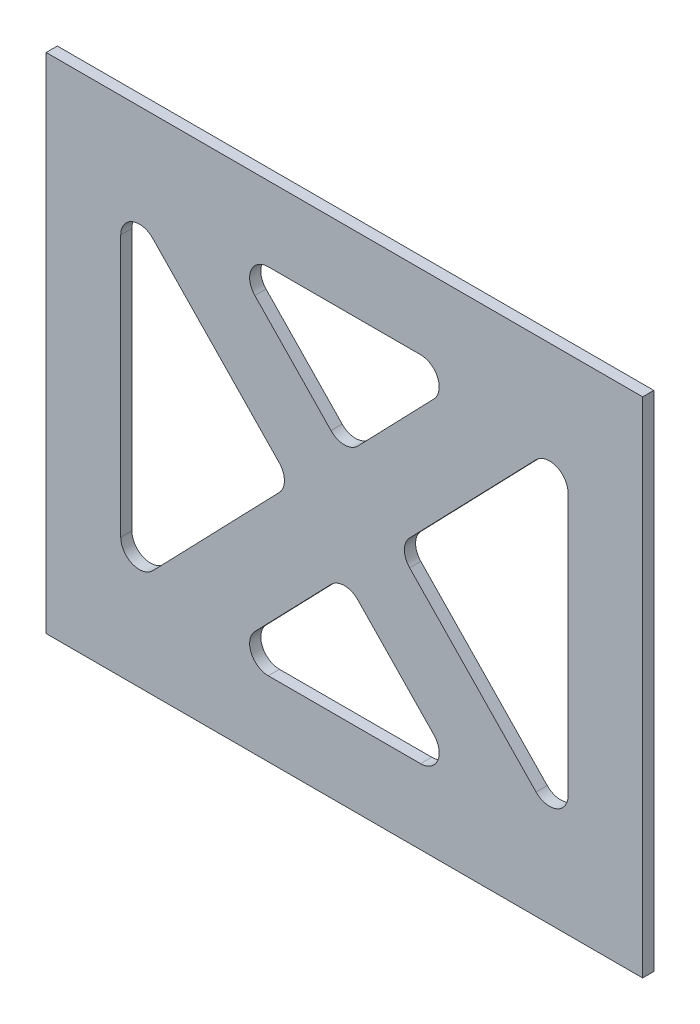
SolidWorks part; units mm, degrees
material "birch 3mm plywood"
ref_plane "Front Plane" through (0, 0, 0) normal (0, 0, 1) x (1, 0, 0)
ref_plane "Top Plane" through (0, 0, 0) normal (0, 1, 0) x (1, 0, 0)
ref_plane "Right Plane" through (0, 0, 0) normal (1, 0, 0) x (0, 0, -1)
sketch "Sketch1" plane through (0, 0, 152) normal (0, 0, 1) x (1, 0, 0)
  line L1 (-80, 80.4171) -> (80, 80.4171)
  line L2 (-80, 80.4171) -> (-80, -54.5829)
  line L3 (-80, -54.5829) -> (80, -54.5829)
  line L4 (80, 80.4171) -> (80, -54.5829)
  line L6 (-60, -22.2046) -> (-60, 48.0389)
  line L7 (-51.4028, 51.5116) -> (-17.4968, 16.3899)
  line L12 (78, -49.5829) -> (-78, -49.5829) construction
  line L13 (78, 75.4171) -> (78, -49.5829) construction
  line L14 (-78, -49.5829) -> (-78, 75.4171) construction
  line L15 (-78, 75.4171) -> (78, 75.4171) construction
  line L18 (20.4243, 60.4171) -> (-20.4243, 60.4171)
  line L19 (-17.4968, 9.4444) -> (-51.4028, -25.6773)
  line L20 (-24.0216, 51.9444) -> (-3.5972, 30.7877)
  line L21 (3.5972, 30.7877) -> (24.0216, 51.9444)
  line L22 (80, 80.4171) -> (80, 77.4171) construction
  line L23 (51.4028, 51.5116) -> (17.4968, 16.3899)
  line L24 (60, -22.2046) -> (60, 48.0389)
  line L25 (17.4968, 9.4444) -> (51.4028, -25.6773)
  line L26 (-78, 12.9171) -> (78, 12.9171) construction
  line L27 (-24.0216, -26.1101) -> (-3.5972, -4.9534)
  line L28 (20.4243, -34.5829) -> (-20.4243, -34.5829)
  line L29 (3.5972, -4.9534) -> (24.0216, -26.1101)
  line L30 (0, 27.0615) -> (0, -1.2272) construction
  line L31 (-14.1443, 12.9171) -> (14.1443, 12.9171) construction
  line L32 (0, 27.0615) -> (0, -1.2272) construction
  line L34 (-80, -54.5829) -> (-80, 77.4171) construction
  line L36 (80, 80.4171) -> (-80, 80.4171) construction
  line L37 (75, -49.5829) -> (-75, -49.5829) construction
  arc A0 (-51.4028, -25.6773) -> (-60, -22.2046) centre (-55, -22.2046) cw
  arc A1 (-17.4968, 9.4444) -> (-17.4968, 16.3899) centre (-21.0941, 12.9171) ccw
  arc A2 (-51.4028, 51.5116) -> (-60, 48.0389) centre (-55, 48.0389) ccw
  arc A3 (24.0216, -26.1101) -> (20.4243, -34.5829) centre (20.4243, -29.5829) cw
  arc A4 (-24.0216, -26.1101) -> (-20.4243, -34.5829) centre (-20.4243, -29.5829) ccw
  arc A5 (-3.5972, -4.9534) -> (3.5972, -4.9534) centre (0, -8.4261) cw
  arc A6 (17.4968, 16.3899) -> (17.4968, 9.4444) centre (21.0941, 12.9171) ccw
  arc A7 (51.4028, -25.6773) -> (60, -22.2046) centre (55, -22.2046) ccw
  arc A8 (60, 48.0389) -> (51.4028, 51.5116) centre (55, 48.0389) ccw
  arc A9 (-24.0216, 51.9444) -> (-20.4243, 60.4171) centre (-20.4243, 55.4171) cw
  arc A10 (24.0216, 51.9444) -> (20.4243, 60.4171) centre (20.4243, 55.4171) ccw
  arc A11 (3.5972, 30.7877) -> (-3.5972, 30.7877) centre (0, 34.2604) cw
  point P14 (0, 12.9171)
  point P15 (0, 12.9171)
  point P32 (-60, 60.4171)
  point P35 (32.201, -34.5829)
  point P38 (-32.201, -34.5829)
  point P51 (-32.201, 60.4171)
  point P54 (32.201, 60.4171)
  dimension "D9" = 5
  dimension "D10" = 5
  dimension "D1" = 2
  dimension "D2" = 2
  dimension "D3" = 5
  dimension "D4" = 5
  dimension "D5" = 20
  dimension "D6" = 20
  dimension "D7" = 20
  dimension "D8" = 20
extrude "Boss-Extrude1" add sketch "Sketch1" along normal blind 3
